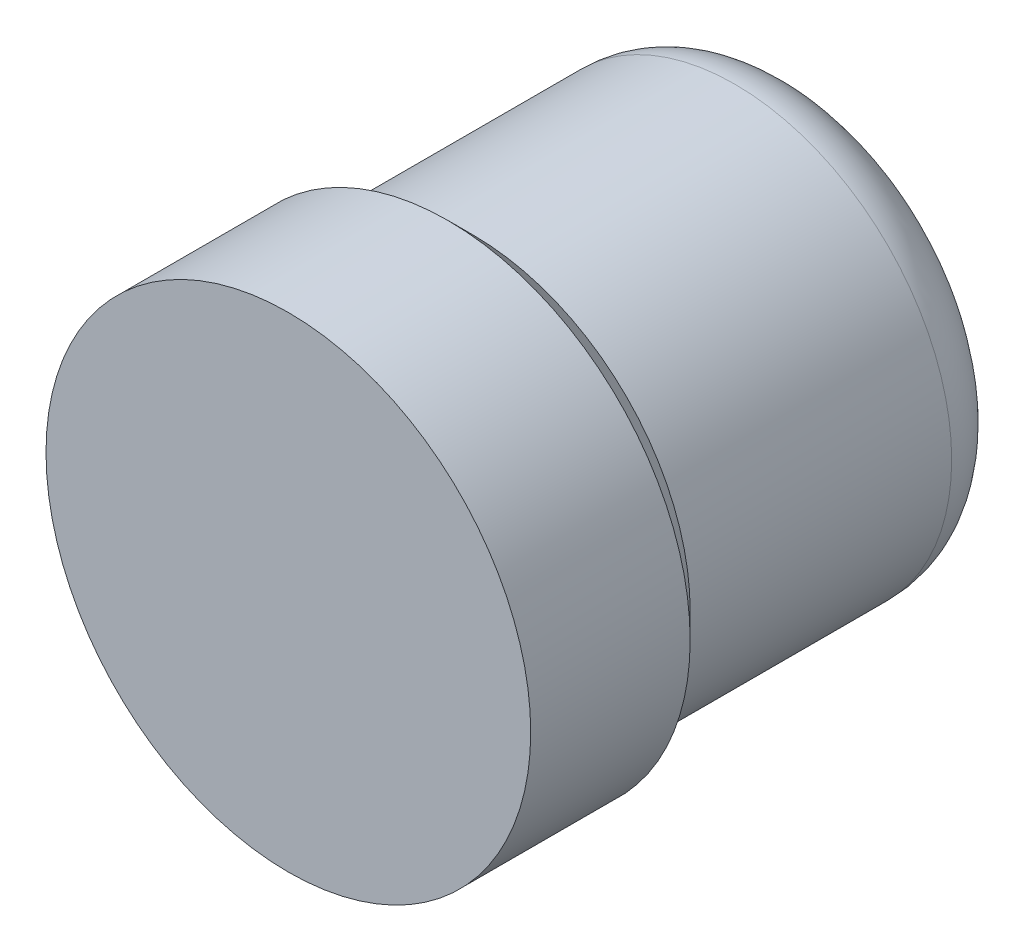
SolidWorks part; units mm, degrees
ref_plane "Front Plane" through (0, 0, 0) normal (0, 0, 1) x (1, 0, 0)
ref_plane "Top Plane" through (0, 0, 0) normal (0, 1, 0) x (1, 0, 0)
ref_plane "Right Plane" through (0, 0, 0) normal (1, 0, 0) x (0, 0, -1)
sketch "Sketch1" plane through (0, 0, 0) normal (0, 0, 1) x (1, 0, 0)
  circle A0 centre (0, 21.5) radius 3.8
  dimension "D1" = 7.6
extrude "Boss-Extrude1" add sketch "Sketch1" against normal blind 3
sketch "Sketch2" plane through (0, 0, -3) normal (0, 0, -1) x (-1, 0, 0)
  circle A0 centre (0, 21.5) radius 3.4
  dimension "D1" = 6.8
extrude "Boss-Extrude2" add sketch "Sketch2" along normal blind 5
fillet "Fillet1" radius 1 1 edges at (-3.4, 21.5, -8)
chamfer "Chamfer1" distance 0.5 angle 45 1 edges at (3.8, 21.5, -3)
